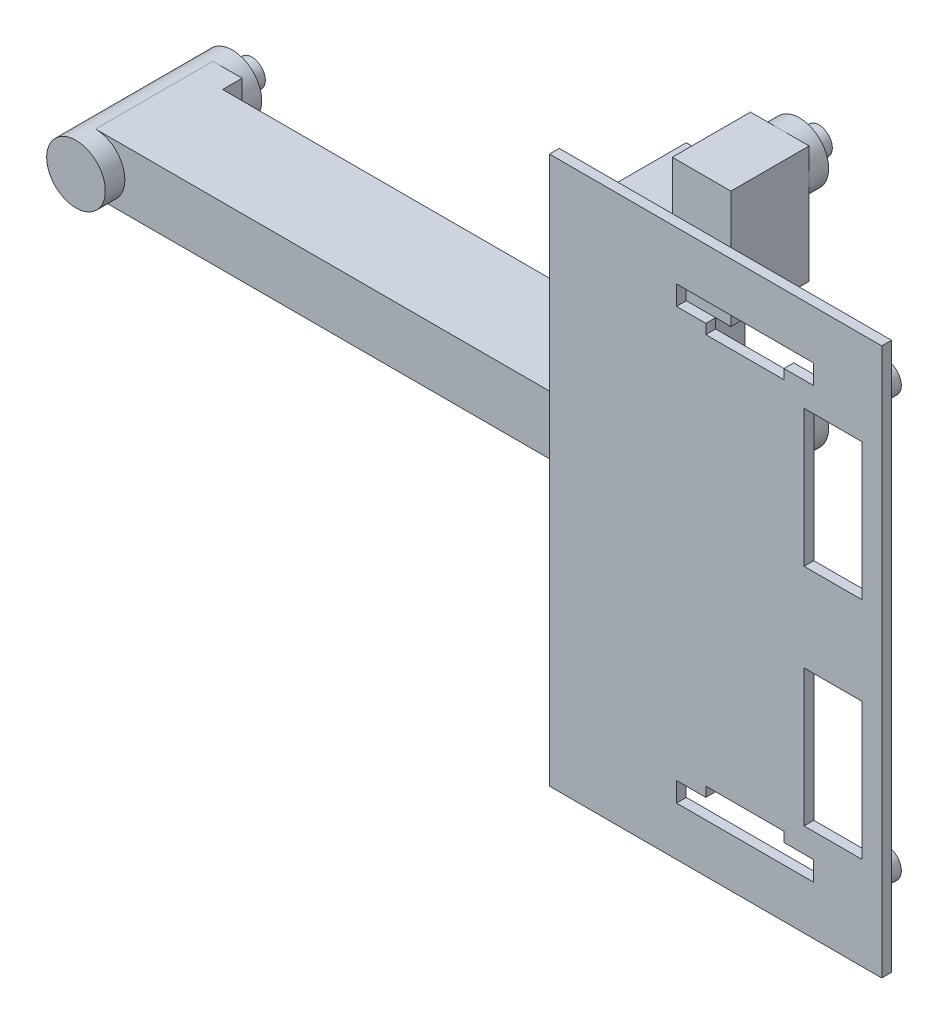
SolidWorks part; units mm, degrees
ref_plane "前视基准面" through (0, 0, 0) normal (0, 0, 1) x (1, 0, 0)
ref_plane "上视基准面" through (0, 0, 0) normal (0, 1, 0) x (1, 0, 0)
ref_plane "右视基准面" through (0, 0, 0) normal (1, 0, 0) x (0, 0, -1)
sketch "草图1" plane through (0, 0, 0) normal (0, 0, 1) x (1, 0, 0)
  line L1 (-32.5, 3) -> (32.5, 3)
  line L2 (-32.5, 3) -> (-32.5, -3)
  line L3 (-32.5, -3) -> (32.5, -3)
  line L4 (32.5, 3) -> (32.5, -3)
  line L5 (-32.5, 3) -> (32.5, -3) construction
  line L6 (-32.5, -3) -> (32.5, 3) construction
  point P0 (0, 0)
  dimension "D1" = 65
  dimension "D2" = 6
extrude "凸台-拉伸1" add sketch "草图1" along normal blind 12
fillet "圆角4" radius 3 1 edges at (-32.5, -3, 6)
fillet "圆角5" radius 3 1 edges at (-32.5, 3, 6)
sketch "草图7" plane through (0, 0, 0) normal (0, 0, -1) x (-1, 0, 0)
  circle A0 centre (29.5, 0) radius 1.375
extrude "凸台-拉伸2" add sketch "草图7" along normal blind 4 contours A0
sketch "草图8" plane through (0, 0, 0) normal (0, 0, -1) x (-1, 0, 0)
  circle A0 centre (29.5, 0) radius 3
extrude "凸台-拉伸3" add sketch "草图8" along normal blind 2
sketch "草图9" plane through (0, 0, 12) normal (0, 0, 1) x (1, 0, 0)
  circle A0 centre (-29.5, 0) radius 3
extrude "凸台-拉伸4" add sketch "草图9" along normal blind 4
sketch "草图10" plane through (0, 0, 0) normal (0, 0, -1) x (-1, 0, 0)
  circle A0 centre (-29.5, 0) radius 3
extrude "凸台-拉伸5" add sketch "草图10" along normal blind 2
sketch "草图11" plane through (0, 0, -2) normal (0, 0, -1) x (-1, 0, 0)
  circle A0 centre (-29.5, 0) radius 1.375
extrude "凸台-拉伸6" add sketch "草图11" along normal blind 2
sketch "草图12" plane through (0, 0, 12) normal (0, 0, 1) x (1, 0, 0)
  line L0 (32.5, -3) -> (32.5, 3)
  line L1 (32.5, -3) -> (26.5, -3)
  line L2 (32.5, 3) -> (26.5, 3)
  line L3 (26.5, -3) -> (26.5, 3)
extrude "凸台-拉伸7" add sketch "草图12" along normal blind 2
sketch "草图13" plane through (0, 0, 0) normal (0, 0, -1) x (-1, 0, 0)
  line L1 (-32.5, -3) -> (-26.5, -3)
  line L2 (-32.5, -3) -> (-32.5, 27)
  line L3 (-32.5, 27) -> (-26.5, 27)
  line L4 (-26.5, -3) -> (-26.5, 27)
  dimension "D1" = 6
  dimension "D2" = 30
extrude "凸台-拉伸8" add sketch "草图13" against normal blind 2
sketch "草图14" plane through (0, 0, 0) normal (0, 0, -1) x (-1, 0, 0)
  circle A0 centre (-29.5, 24) radius 3
extrude "凸台-拉伸9" add sketch "草图14" along normal blind 2
sketch "草图15" plane through (0, 0, 0) normal (0, 0, -1) x (-1, 0, 0)
  circle A0 centre (-29.5, 24) radius 1.375
extrude "凸台-拉伸10" add sketch "草图15" along normal blind 4
sketch "草图18" plane through (0, 0, 12) normal (0, 0, 1) x (1, 0, 0)
  line L0 (32.5, -3) -> (32.5, 3) construction
  line L1 (18.93, 27) -> (24.93, 27)
  line L2 (18.93, 27) -> (18.93, -3)
  line L3 (18.93, -3) -> (24.93, -3)
  line L4 (24.93, 27) -> (24.93, -3)
  line L5 (18.93, 27) -> (24.93, -3) construction
  line L6 (18.93, -3) -> (24.93, 27) construction
  line L7 (26.5, -3) -> (32.5, -3) construction
  point P0 (21.93, 12)
  point P9 (21.93, -3)
  dimension "D1" = 30
  dimension "D2" = 6
  dimension "D3" = 7.57
  dimension "D4" = 0
extrude "凸台-拉伸11" add sketch "草图18" along normal blind 4
sketch "草图19" plane through (0, 0, 12) normal (0, 0, -1) x (-1, 0, 0)
  line L1 (-18.93, 27) -> (-24.93, 27)
  line L2 (-18.93, 27) -> (-18.93, -3)
  line L3 (-18.93, -3) -> (-24.93, -3)
  line L4 (-24.93, 27) -> (-24.93, -3)
extrude "凸台-拉伸12" add sketch "草图19" along normal blind 10
sketch "草图29" plane through (0, 0, 16) normal (0, 0, 1) x (1, 0, 0)
  line L1 (24.93, 27) -> (-43.8103, 27)
  line L2 (24.93, 27) -> (24.93, -9.6985)
  line L3 (24.93, -9.6985) -> (-43.8103, -9.6985)
  line L4 (-43.8103, 27) -> (-43.8103, -9.6985)
extrude "切除-拉伸3" cut sketch "草图29" against normal blind 2
sketch "草图30" plane through (0, 0, 14) normal (0, 0, 1) x (1, 0, 0)
  line L1 (32.5, -3) -> (24.93, -3)
  line L2 (32.5, -3) -> (32.5, 3)
  line L3 (32.5, 3) -> (24.93, 3)
  line L4 (24.93, -3) -> (24.93, 3)
extrude "切除-拉伸4" cut sketch "草图30" against normal blind 12
sketch "草图31" plane through (0, 0, 2) normal (0, 0, -1) x (-1, 0, 0)
  line L1 (-18.93, 27) -> (-26.5, 27)
  line L2 (-18.93, 27) -> (-18.93, 3)
  line L3 (-18.93, 3) -> (-26.5, 3)
  line L4 (-26.5, 27) -> (-26.5, 3)
extrude "凸台-拉伸18" add sketch "草图31" along normal blind 2
sketch "草图32" plane through (0, 0, 0) normal (0, 0, -1) x (-1, 0, 0)
  line L0 (-32.5, 0) -> (-32.5, 24) construction
  line L1 (-32.5, 21) -> (-26.5, 21)
  line L2 (-32.5, 21) -> (-32.5, 3)
  line L3 (-32.5, 3) -> (-26.5, 3)
  line L4 (-26.5, 21) -> (-26.5, 3)
  circle A0 centre (-29.5, 24) radius 3 construction
  dimension "D3" = 3
  dimension "D1" = 6
  dimension "D2" = 18
extrude "切除-拉伸6" cut sketch "草图32" against normal blind 2
sketch "草图33" plane through (0, 0, 2) normal (0, 0, 1) x (1, 0, 0)
  line L0 (24.93, 27) -> (24.93, -3) construction
  line L1 (26.5, 21) -> (24.93, 21)
  line L2 (26.5, 21) -> (26.5, 3)
  line L3 (26.5, 3) -> (24.93, 3)
  line L4 (24.93, 21) -> (24.93, 3)
  dimension "D1" = 18
extrude "切除-拉伸7" cut sketch "草图33" against normal blind 2
sketch "草图34" plane through (0, 0, 14) normal (0, 0, 1) x (1, 0, 0)
  line L1 (18.93, 27) -> (52.93, 27)
  line L2 (18.93, 27) -> (18.93, -23)
  line L3 (18.93, -23) -> (52.93, -23)
  line L4 (52.93, 27) -> (52.93, -23)
  dimension "D1" = 50
  dimension "D2" = 34
extrude "凸台-拉伸19" add sketch "草图34" against normal blind 1
sketch "草图35" plane through (0, 0, 13) normal (0, 0, -1) x (-1, 0, 0)
  line L0 (-52.93, 27) -> (-24.93, 27) construction
  line L1 (-52.93, -23) -> (-52.93, 27) construction
  line L2 (-18.93, -23) -> (-52.93, -23) construction
  line L3 (-18.93, -3) -> (-18.93, -23) construction
  circle A0 centre (-49.43, 23.5) radius 1.5
  circle A1 centre (-49.43, -19.5) radius 1.5
  circle A2 centre (-28.43, -19.5) radius 1.5
  circle A3 centre (-28.43, 23.5) radius 1.5
  dimension "D1" = 3.5
  dimension "D3" = 3.5
  dimension "D5" = 9.5
  dimension "D2" = 3.5
  dimension "D4" = 3.5
extrude "凸台-拉伸20" add sketch "草图35" along normal blind 2
sketch "草图36" plane through (0, 0, 13) normal (0, 0, -1) x (-1, 0, 0)
  line L0 (-52.93, 27) -> (-24.93, 27) construction
  line L1 (-47.93, 27) -> (-29.93, 27)
  line L2 (-47.93, 27) -> (-47.93, 23)
  line L3 (-47.93, 23) -> (-29.93, 23)
  line L4 (-29.93, 27) -> (-29.93, 23)
  circle A0 centre (-49.43, 23.5) radius 1.5 construction
  circle A1 centre (-28.43, -19.5) radius 1.5 construction
  dimension "D1" = 1.5
  dimension "D2" = 1.5
  dimension "D3" = 4
extrude "切除-拉伸8" cut sketch "草图36" against normal blind 3
sketch "草图37" plane through (0, 0, 13) normal (0, 0, -1) x (-1, 0, 0)
  line L0 (-29.93, -23) -> (-47.93, -23)
  line L1 (-29.93, -23) -> (-29.93, -19)
  line L2 (-47.93, -23) -> (-47.93, -19)
  line L3 (-29.93, -19) -> (-47.93, -19)
  line L4 (-18.93, -23) -> (-52.93, -23) construction
  dimension "D1" = 4
extrude "切除-拉伸9" cut sketch "草图37" against normal blind 3
sketch "草图38" plane through (0, 0, 13) normal (0, 0, -1) x (-1, 0, 0)
  line L0 (-52.93, -23) -> (-52.93, 27) construction
  line L1 (-52.93, 20.5) -> (-44.9804, 20.5)
  line L2 (-52.93, 20.5) -> (-52.93, -16.5)
  line L3 (-52.93, -16.5) -> (-44.9804, -16.5)
  line L4 (-44.9804, 20.5) -> (-44.9804, -16.5)
  circle A0 centre (-49.43, 23.5) radius 1.5 construction
  circle A1 centre (-49.43, -19.5) radius 1.5 construction
  dimension "D2" = 3
  dimension "D1" = 3
extrude "切除-拉伸10" cut sketch "草图38" against normal blind 3
sketch "草图39" plane through (0, 0, 13) normal (0, 0, -1) x (-1, 0, 0)
  line L1 (-52.93, 20.5) -> (-50.93, 20.5)
  line L2 (-52.93, 20.5) -> (-52.93, -18.2774)
  line L3 (-52.93, -18.2774) -> (-50.93, -18.2774)
  line L4 (-50.93, 20.5) -> (-50.93, -18.2774)
extrude "凸台-拉伸21" add sketch "草图39" against normal blind 1
sketch "草图40" plane through (0, 0, 13) normal (0, 0, -1) x (-1, 0, 0)
  line L1 (-47.93, 27) -> (-28.0386, 27)
  line L2 (-47.93, 27) -> (-47.93, 25)
  line L3 (-47.93, 25) -> (-28.0386, 25)
  line L4 (-28.0386, 27) -> (-28.0386, 25)
extrude "凸台-拉伸22" add sketch "草图40" against normal blind 1
sketch "草图41" plane through (0, 0, 13) normal (0, 0, -1) x (-1, 0, 0)
  line L0 (-47.93, -19.5) -> (-47.93, -23) construction
  line L1 (-47.93, -21) -> (-29.93, -21)
  line L2 (-47.93, -21) -> (-47.93, -23)
  line L3 (-47.93, -23) -> (-29.93, -23)
  line L4 (-29.93, -21) -> (-29.93, -23)
extrude "凸台-拉伸23" add sketch "草图41" against normal blind 1
sketch "草图42" plane through (0, 0, 13) normal (0, 0, -1) x (-1, 0, 0)
  line L0 (-50.93, -16.5) -> (-50.93, 20.5) construction
  line L1 (-50.93, 5.3498) -> (-44.9804, 5.3498)
  line L2 (-50.93, 5.3498) -> (-50.93, -2.4362)
  line L3 (-50.93, -2.4362) -> (-44.9804, -2.4362)
  line L4 (-44.9804, 5.3498) -> (-44.9804, -2.4362)
  line L5 (-44.9804, -16.5) -> (-44.9804, 20.5) construction
extrude "凸台-拉伸24" add sketch "草图42" against normal blind 1
sketch "草图43" plane through (0, 0, 13) normal (0, 0, -1) x (-1, 0, 0)
  line L0 (-29.93, -21) -> (-47.93, -21) construction
  line L1 (-47.93, -19) -> (-45.93, -19)
  line L2 (-47.93, -19) -> (-47.93, -21)
  line L3 (-47.93, -21) -> (-45.93, -21)
  line L4 (-45.93, -19) -> (-45.93, -21)
  line L5 (-47.93, 23) -> (-29.93, 23) construction
  line L6 (-29.93, -19) -> (-31.93, -19)
  line L7 (-29.93, -19) -> (-29.93, -21)
  line L8 (-29.93, -21) -> (-31.93, -21)
  line L9 (-31.93, -19) -> (-31.93, -21)
  line L10 (-47.93, 25) -> (-45.93, 25)
  line L11 (-47.93, 25) -> (-47.93, 23)
  line L12 (-47.93, 23) -> (-45.93, 23)
  line L13 (-45.93, 25) -> (-45.93, 23)
  line L15 (-29.93, 25) -> (-31.93, 25)
  line L16 (-29.93, 25) -> (-29.93, 23)
  line L17 (-29.93, 23) -> (-31.93, 23)
  line L18 (-31.93, 25) -> (-31.93, 23)
  dimension "D1" = 2
  dimension "D2" = 2
  dimension "D3" = 2
  dimension "D4" = 2
extrude "凸台-拉伸25" add sketch "草图43" against normal blind 1
sketch "草图44" plane through (0, 0, 13) normal (0, 0, -1) x (-1, 0, 0)
  line L1 (-52.93, -23) -> (-18.93, -23)
  line L2 (-52.93, -23) -> (-52.93, -29)
  line L3 (-52.93, -29) -> (-18.93, -29)
  line L4 (-18.93, -23) -> (-18.93, -29)
  dimension "D1" = 6
extrude "凸台-拉伸26" add sketch "草图44" against normal blind 1
sketch "草图45" plane through (0, 0, 14) normal (0, 0, 1) x (1, 0, 0)
  line L2 (44.9804, 5.3498) -> (44.9804, 20.5) construction
  line L3 (50.93, 5.3498) -> (44.9804, 5.3498)
  line L4 (50.93, 5.3498) -> (50.93, 6.5)
  line L5 (50.93, 6.5) -> (44.9804, 6.5)
  line L6 (44.9804, 5.3498) -> (44.9804, 6.5)
  line L7 (44.9804, 20.5) -> (50.93, 20.5) construction
  line L8 (50.93, -16.5) -> (50.93, -2.4362) construction
  line L10 (44.9804, -2.4362) -> (50.93, -2.4362)
  line L11 (44.9804, -2.4362) -> (44.9804, -2.5)
  line L12 (44.9804, -2.5) -> (50.93, -2.5)
  line L13 (50.93, -2.4362) -> (50.93, -2.5)
  dimension "D1" = 14
  dimension "D2" = 14
extrude "凸台-拉伸27" add sketch "草图45" against normal blind 1
sketch "草图46" plane through (0, 0, 14) normal (0, 0, 1) x (1, 0, 0)
  line L0 (45.93, 23) -> (31.93, 23) construction
  line L1 (35.43, 23) -> (42.43, 23)
  line L2 (35.43, 23) -> (35.43, 22)
  line L3 (35.43, 22) -> (42.43, 22)
  line L4 (42.43, 23) -> (42.43, 22)
  line L5 (31.93, 25) -> (31.93, 23) construction
  line L6 (31.93, -19) -> (45.93, -19) construction
  line L7 (35.43, -19) -> (42.43, -19)
  line L8 (35.43, -19) -> (35.43, -18)
  line L9 (35.43, -18) -> (42.43, -18)
  line L10 (42.43, -19) -> (42.43, -18)
  line L11 (45.93, -21) -> (45.93, -19) construction
  dimension "D1" = 3.5
  dimension "D2" = 3.5
  dimension "D3" = 7
  dimension "D4" = 1
  dimension "D5" = 7
  dimension "D6" = 3.5
  dimension "D7" = 1
extrude "切除-拉伸11" cut sketch "草图46" against normal blind 11
sketch "草图47" plane through (0, 0, 2) normal (0, 0, 1) x (1, 0, 0)
  line L0 (24.93, 21) -> (32.5, 21) construction
  line L1 (24.93, 27) -> (29.93, 27)
  line L2 (24.93, 27) -> (24.93, 21)
  line L3 (24.93, 21) -> (29.93, 21)
  line L4 (29.93, 27) -> (29.93, 21)
  dimension "D1" = 5
extrude "凸台-拉伸28" add sketch "草图47" along normal blind 7
sketch "草图48" plane through (0, 0, 2) normal (0, 0, 1) x (1, 0, 0)
  line L1 (24.93, 3) -> (32.5, 3)
  line L2 (24.93, 3) -> (24.93, -3)
  line L3 (24.93, -3) -> (32.5, -3)
  line L4 (32.5, 3) -> (32.5, -3)
extrude "凸台-拉伸29" add sketch "草图48" along normal blind 2
sketch "草图49" plane through (0, 0, 13) normal (0, 0, -1) x (-1, 0, 0)
  line L0 (-45.93, -21) -> (-45.93, -19) construction
  line L1 (-45.93, -25) -> (-31.93, -25)
  line L2 (-45.93, -25) -> (-45.93, -23)
  line L3 (-45.93, -23) -> (-31.93, -23)
  line L4 (-31.93, -25) -> (-31.93, -23)
  line L5 (-31.93, -21) -> (-45.93, -21) construction
  line L6 (-31.93, -19) -> (-31.93, -21) construction
  line L7 (-42.43, -19) -> (-42.43, -18) construction
  line L8 (-35.43, -18) -> (-35.43, -19) construction
  line L9 (-42.43, -22) -> (-35.43, -22)
  line L10 (-42.43, -22) -> (-42.43, -23)
  line L11 (-42.43, -23) -> (-35.43, -23)
  line L12 (-35.43, -22) -> (-35.43, -23)
  line L13 (-42.43, 22) -> (-42.43, 23) construction
  line L14 (-35.43, 22) -> (-42.43, 22) construction
  line L15 (-42.43, 19) -> (-35.43, 19)
  line L16 (-42.43, 19) -> (-42.43, 18)
  line L17 (-42.43, 18) -> (-35.43, 18)
  line L18 (-35.43, 19) -> (-35.43, 18)
  line L19 (-45.93, 23) -> (-45.93, 25) construction
  line L20 (-45.93, 21) -> (-31.93, 21)
  line L21 (-45.93, 21) -> (-45.93, 19)
  line L22 (-45.93, 19) -> (-31.93, 19)
  line L23 (-31.93, 21) -> (-31.93, 19)
  line L24 (-31.93, 25) -> (-31.93, 23) construction
  line L25 (-50.93, -16.5) -> (-50.93, -2.5) construction
  line L26 (-44.9804, -16.5) -> (-44.9804, -2.5) construction
  line L27 (-50.93, -6.5) -> (-44.9804, -6.5)
  line L28 (-50.93, -6.5) -> (-50.93, -20.5)
  line L29 (-50.93, -20.5) -> (-44.9804, -20.5)
  line L30 (-44.9804, -6.5) -> (-44.9804, -20.5)
  line L31 (-44.9804, -2.5) -> (-50.93, -2.5) construction
  line L32 (-50.93, 6.5) -> (-50.93, 20.5) construction
  line L33 (-44.9804, 6.5) -> (-44.9804, 20.5) construction
  line L34 (-50.93, 16.5) -> (-44.9804, 16.5)
  line L35 (-50.93, 16.5) -> (-50.93, 2.5)
  line L36 (-50.93, 2.5) -> (-44.9804, 2.5)
  line L37 (-44.9804, 16.5) -> (-44.9804, 2.5)
  line L38 (-44.9804, 20.5) -> (-50.93, 20.5) construction
  point P6 (-45.93, -24)
  dimension "D1" = 0
  dimension "D2" = 2
  dimension "D3" = 4
  dimension "D4" = 0
  dimension "D5" = 1
  dimension "D6" = 0
  dimension "D7" = 1
  dimension "D8" = 4
  dimension "D9" = 2
  dimension "D10" = 0
  dimension "D11" = 14
  dimension "D12" = 4
  dimension "D13" = 14
  dimension "D14" = 4
sketch "草图50" plane through (0, 0, 13) normal (0, 0, -1) x (-1, 0, 0)
  line L1 (-51.68, 26.3114) -> (-25.0024, 26.3114)
  line L2 (-51.68, 26.3114) -> (-51.68, -25.1125)
  line L3 (-51.68, -25.1125) -> (-25.0024, -25.1125)
  line L4 (-25.0024, 26.3114) -> (-25.0024, -25.1125)
extrude "凸台-拉伸35" add sketch "草图50" against normal blind 1
sketch "草图52" plane through (0, 0, 13) normal (0, 0, -1) x (-1, 0, 0)
  circle A0 centre (-49.43, 19.5) radius 1.5
  circle A1 centre (-49.43, 23.5) radius 1.5 construction
  circle A2 centre (-28.43, 19.5) radius 1.5
  circle A3 centre (-49.43, -23.5) radius 1.5
  circle A4 centre (-49.43, -19.5) radius 1.5 construction
  circle A5 centre (-28.43, -23.5) radius 1.5
  dimension "D1" = 4
  dimension "D2" = 4
sketch "草图53" plane through (0, 0, 13) normal (0, 0, -1) x (-1, 0, 0)
  line L1 (-52.0421, 25.8285) -> (-23.4934, 25.8285)
  line L2 (-52.0421, 25.8285) -> (-52.0421, -26.0782)
  line L3 (-52.0421, -26.0782) -> (-23.4934, -26.0782)
  line L4 (-23.4934, 25.8285) -> (-23.4934, -26.0782)
extrude "切除-拉伸21" cut sketch "草图53" along normal blind 2
extrude "凸台-拉伸37" add sketch "草图52" along normal blind 2
extrude "切除-拉伸22" cut sketch "草图49" against normal blind 4
sketch "草图55" plane through (24.93, 0, 0) normal (1, 0, 0) x (0, 0, -1)
  line L0 (-13, 25.8285) -> (-13, 27) construction
  line L1 (-11, -3) -> (-13, -3)
  line L2 (-11, -3) -> (-11, 26.4143)
  line L3 (-11, 26.4143) -> (-13, 26.4143)
  line L4 (-13, -3) -> (-13, 26.4143)
extrude "凸台-拉伸40" add sketch "草图55" against normal blind 4
sketch "草图57" plane through (0, 0, 13) normal (0, 0, -1) x (-1, 0, 0)
  circle A0 centre (-49.4344, 20.5) radius 1.5
  circle A1 centre (-49.43, 19.5) radius 1.5 construction
  circle A2 centre (-28.4344, 20.5) radius 1.5
  circle A3 centre (-28.43, 19.5) radius 1.5 construction
  circle A4 centre (-28.43, 19.5) radius 1.5 construction
  circle A5 centre (-28.4323, -22.5) radius 1.5
  circle A6 centre (-28.43, -23.5) radius 1.5 construction
  circle A7 centre (-49.4344, -22.5) radius 1.5
  dimension "D1" = 1
  dimension "D2" = 1
  dimension "D3" = 21
  dimension "D4" = 1
  dimension "D5" = 1
sketch "草图58" plane through (0, 0, 13) normal (0, 0, -1) x (-1, 0, 0)
  line L1 (-25.787, -28.3114) -> (-51.3782, -28.3114)
  line L2 (-25.787, -28.3114) -> (-25.787, 22.6296)
  line L3 (-25.787, 22.6296) -> (-51.3782, 22.6296)
  line L4 (-51.3782, -28.3114) -> (-51.3782, 22.6296)
extrude "切除-拉伸23" cut sketch "草图58" along normal blind 4
extrude "凸台-拉伸41" add sketch "草图57" along normal blind 2
sketch "草图59" plane through (0, 0, 13) normal (0, 0, -1) x (-1, 0, 0)
  line L0 (-44.9804, -6.5) -> (-44.9804, -20.5) construction
  line L1 (-44.9804, -19.5) -> (-50.93, -19.5)
  line L2 (-44.9804, -19.5) -> (-44.9804, -5.5)
  line L3 (-44.9804, -5.5) -> (-50.93, -5.5)
  line L4 (-50.93, -19.5) -> (-50.93, -5.5)
  line L5 (-50.93, -20.5) -> (-50.93, -6.5) construction
  line L6 (-50.93, -20.5) -> (-44.9804, -20.5) construction
  line L7 (-44.9804, 16.5) -> (-44.9804, 2.5) construction
  line L8 (-44.9804, 3.5) -> (-50.93, 3.5)
  line L9 (-44.9804, 3.5) -> (-44.9804, 17.5)
  line L10 (-44.9804, 17.5) -> (-50.93, 17.5)
  line L11 (-50.93, 3.5) -> (-50.93, 17.5)
  line L12 (-50.93, 2.5) -> (-50.93, 16.5) construction
  line L13 (-50.93, 2.5) -> (-44.9804, 2.5) construction
  line L14 (-45.93, 21) -> (-45.93, 19) construction
  line L15 (-31.93, 21) -> (-31.93, 19) construction
  line L16 (-45.93, 20) -> (-31.93, 20)
  line L17 (-45.93, 20) -> (-45.93, 22)
  line L18 (-45.93, 22) -> (-31.93, 22)
  line L19 (-31.93, 20) -> (-31.93, 22)
  line L20 (-45.93, 21) -> (-31.93, 21) construction
  line L21 (-45.93, 19) -> (-42.43, 19) construction
  line L22 (-35.43, 19) -> (-35.43, 18) construction
  line L23 (-42.43, 19) -> (-35.43, 19)
  line L24 (-42.43, 19) -> (-42.43, 20)
  line L25 (-42.43, 20) -> (-35.43, 20)
  line L26 (-35.43, 19) -> (-35.43, 20)
  line L27 (-31.93, -25) -> (-31.93, -23) construction
  line L28 (-31.93, -24) -> (-45.93, -24)
  line L29 (-31.93, -24) -> (-31.93, -22)
  line L30 (-31.93, -22) -> (-45.93, -22)
  line L31 (-45.93, -24) -> (-45.93, -22)
  line L32 (-45.93, -25) -> (-45.93, -23) construction
  line L33 (-45.93, -25) -> (-31.93, -25) construction
  line L34 (-45.93, -23) -> (-42.43, -23) construction
  line L35 (-42.43, -22) -> (-42.43, -23) construction
  line L36 (-35.43, -22) -> (-42.43, -22)
  line L37 (-35.43, -22) -> (-35.43, -21)
  line L38 (-35.43, -21) -> (-42.43, -21)
  line L39 (-42.43, -22) -> (-42.43, -21)
  line L40 (-35.43, -22) -> (-35.43, -23) construction
  dimension "D1" = 14
  dimension "D2" = 1
  dimension "D3" = 14
  dimension "D4" = 1
  dimension "D5" = 1
  dimension "D6" = 1
  dimension "D7" = 0
  dimension "D8" = 1
  dimension "D9" = 1
  dimension "D10" = 0
  dimension "D11" = 0
  dimension "D12" = 0
  dimension "D13" = 1
sketch "草图60" plane through (0, 0, 13) normal (0, 0, -1) x (-1, 0, 0)
  line L1 (-52.4043, 25.2853) -> (-26.2699, 25.2853)
  line L2 (-52.4043, 25.2853) -> (-52.4043, -26.9835)
  line L3 (-52.4043, -26.9835) -> (-26.2699, -26.9835)
  line L4 (-26.2699, 25.2853) -> (-26.2699, -26.9835)
extrude "凸台-拉伸43" add sketch "草图60" against normal blind 1
extrude "切除-拉伸24" cut sketch "草图59" against normal blind 1
sketch "草图62" plane through (0, 0, 0) normal (0, 0, -1) x (-1, 0, 0)
  circle A0 centre (-28.5, 0) radius 3
  circle A1 centre (-29.5, 0) radius 1.375 construction
  dimension "D1" = 1
sketch "草图63" plane through (0, 0, 0) normal (0, 0, -1) x (-1, 0, 0)
  line L0 (-18.93, 27) -> (-29.5, 27) construction
  circle A0 centre (-28.5, 24) radius 3
  circle A1 centre (-29.5, 24) radius 3 construction
  dimension "D1" = 3
  dimension "D2" = 1
sketch "草图64" plane through (0, -3, 0) normal (0, -1, 0) x (1, 0, 0)
  line L0 (32.5, -2) -> (32.5, 0) construction
  line L1 (32.5, 0) -> (-22.296, 0)
  line L2 (32.5, 0) -> (32.5, -10.1972)
  line L3 (32.5, -10.1972) -> (-22.296, -10.1972)
  line L4 (-22.296, 0) -> (-22.296, -10.1972)
  line L5 (-29.5, 0) -> (29.5, 0) construction
  dimension "D1" = 0
extrude "切除-拉伸25" cut sketch "草图64" against normal blind 43
extrude "凸台-拉伸44" add sketch "草图62" along normal blind 2
extrude "凸台-拉伸45" add sketch "草图63" along normal blind 2 contours A0
sketch "草图65" plane through (0, 0, -2) normal (0, 0, -1) x (-1, 0, 0)
  circle A0 centre (-28.5, 24) radius 1.375
  circle A1 centre (-28.5, 24) radius 3 construction
  circle A3 centre (-28.5, 0) radius 3 construction
  circle A4 centre (29.5, 0) radius 3 construction
  circle A5 centre (-28.5, 0) radius 1.375
  dimension "D1" = 0
  dimension "D2" = 58
  dimension "D3" = 0
extrude "凸台-拉伸46" add sketch "草图65" along normal blind 2
sketch "草图66" plane through (0, 0, 0) normal (0, 0, -1) x (-1, 0, 0)
  line L0 (-28.5, 27) -> (-32.5, 27) construction
  line L1 (-32.5, -3) -> (-31.5, -3)
  line L2 (-32.5, -3) -> (-32.5, 27)
  line L3 (-32.5, 27) -> (-31.5, 27)
  line L4 (-31.5, -3) -> (-31.5, 27)
  dimension "D1" = 3
extrude "切除-拉伸26" cut sketch "草图66" against normal blind 5
sketch "草图67" plane through (0, 0, 0) normal (0, 0, -1) x (-1, 0, 0)
  line L0 (-18.93, 27) -> (-28.5, 27) construction
  line L1 (-25.5, 27) -> (-18.93, 27)
  line L2 (-25.5, 27) -> (-25.5, 21)
  line L3 (-25.5, 21) -> (-18.93, 21)
  line L4 (-18.93, 27) -> (-18.93, 21)
  line L5 (-18.93, 3) -> (-18.93, 27) construction
  circle A0 centre (-28.5, 24) radius 1.375 construction
  circle A1 centre (-28.5, 24) radius 3 construction
  dimension "D1" = 3
  dimension "D2" = 3
sketch "草图68" plane through (0, 27, 0) normal (0, 1, 0) x (1, 0, 0)
  line L1 (24.93, -9) -> (31.5, -9)
  line L2 (24.93, -9) -> (24.93, 0)
  line L3 (24.93, 0) -> (31.5, 0)
  line L4 (31.5, -9) -> (31.5, 0)
extrude "凸台-拉伸47" add sketch "草图68" against normal blind 12
extrude "切除-拉伸29" cut sketch "草图67" against normal blind 13 contours L3 L4 L1 L2
sketch "草图70" plane through (0, -3, 0) normal (0, -1, 0) x (1, 0, 0)
  line L0 (-29.5, 0) -> (28.5, 0) construction
  line L1 (24.93, 13) -> (18.93, 13)
  line L2 (24.93, 13) -> (24.93, 0)
  line L3 (24.93, 0) -> (18.93, 0)
  line L4 (18.93, 13) -> (18.93, 0)
  line L6 (18.93, 12) -> (-29.5, 12)
  line L7 (18.93, 12) -> (18.93, 0)
  line L8 (18.93, 0) -> (-29.5, 0)
  line L9 (-29.5, 12) -> (-29.5, 0)
  line M4 (24.93, 4) -> (24.93, 13)
  line M5 (24.93, 13) -> (18.93, 13)
  line M6 (18.93, 13) -> (18.93, 12)
  line M7 (18.93, 12) -> (-29.5, 12)
  line M8 (-29.5, 12) -> (-29.5, 0)
  line M9 (-29.5, 0) -> (28.5, 0)
extrude "凸台-拉伸48" add sketch "草图70" against normal blind 7 contours L4 L2 M6 M9 M4 M5 | L4 M7 M8 M9
sketch "草图71" plane through (0, 3, 0) normal (0, 1, 0) x (1, 0, 0)
  line L1 (31.5, -4) -> (24.93, -4)
  line L2 (31.5, -4) -> (31.5, 0)
  line L3 (31.5, 0) -> (24.93, 0)
  line L4 (24.93, -4) -> (24.93, 0)
extrude "凸台-拉伸49" add sketch "草图71" along normal blind 1
sketch "草图72" plane through (0, 0, 0) normal (0, 0, -1) x (-1, 0, 0)
  line L0 (-31.5, -3) -> (-31.5, 0) construction
  line L1 (-31.5, 4) -> (-24.93, 4) construction
  circle A0 centre (-28.5, 1) radius 3
  dimension "D1" = 3
  dimension "D2" = 3
sketch "草图73" plane through (0, 0, 0) normal (0, 0, -1) x (-1, 0, 0)
  line L0 (29.5, 4) -> (29.5, 3) construction
  circle A0 centre (29.5, 1) radius 3
  dimension "D1" = 0
sketch "草图74" plane through (0, 0, 14) normal (0, 0, 1) x (1, 0, 0)
  circle A0 centre (-29.5, 0) radius 3
extrude "切除-拉伸30" cut sketch "草图74" against normal blind 32
sketch "草图75" plane through (0, 0, 0) normal (0, 0, -1) x (-1, 0, 0)
  line L0 (29.5, 4) -> (-18.93, 4) construction
  line L1 (29.5, -3) -> (26.367, -3)
  line L2 (29.5, -3) -> (29.5, 4)
  line L3 (29.5, 4) -> (26.367, 4)
  line L4 (26.367, -3) -> (26.367, 4)
  line L5 (29.5, -3) -> (-28.5, -3) construction
  dimension "D1" = 0
extrude "凸台-拉伸51" add sketch "草图75" against normal blind 12
sketch "草图76" plane through (31.5, 0, 0) normal (1, 0, 0) x (0, 0, -1)
  line L1 (0, 4) -> (8.5906, 4)
  line L2 (0, 4) -> (0, -5.1135)
  line L3 (0, -5.1135) -> (8.5906, -5.1135)
  line L4 (8.5906, 4) -> (8.5906, -5.1135)
extrude "切除-拉伸31" cut sketch "草图76" against normal blind 12
sketch "草图77" plane through (31.5, 0, 0) normal (1, 0, 0) x (0, 0, -1)
  line L0 (-13, -3) -> (-13, 21) construction
  line L1 (0, -3) -> (-13, -3)
  line L2 (0, -3) -> (0, -2)
  line L3 (0, -2) -> (-13, -2)
  line L4 (-13, -3) -> (-13, -2)
  dimension "D1" = 1
extrude "切除-拉伸32" cut sketch "草图77" against normal blind 124
extrude "凸台-拉伸52" add sketch "草图72" along normal blind 2
extrude "凸台-拉伸53" add sketch "草图73" against normal blind 14 and the other way blind 2 contours A0
sketch "草图78" plane through (0, 0, -2) normal (0, 0, -1) x (-1, 0, 0)
  circle A1 centre (-28.5, 1) radius 1.375
  circle A2 centre (29.5, 1) radius 1.375
extrude "凸台-拉伸54" add sketch "草图78" along normal blind 2
sketch "草图79" plane through (0, 0, 0) normal (0, 0, -1) x (-1, 0, 0)
  line L0 (-28.5, 4) -> (-24.93, 4) construction
  line L1 (-25.5, 4) -> (26.5, 4)
  line L2 (-25.5, 4) -> (-25.5, -2)
  line L3 (-25.5, -2) -> (26.5, -2)
  line L4 (26.5, 4) -> (26.5, -2)
  line L5 (29.5, -2) -> (-28.5, -2) construction
  circle A0 centre (29.5, 1) radius 1.375 construction
  circle A1 centre (-28.5, 1) radius 1.375 construction
  dimension "D2" = 3
  dimension "D1" = 3
extrude "切除-拉伸33" cut sketch "草图79" against normal blind 2
sketch "草图80" plane through (0, 0, 2) normal (0, 0, -1) x (-1, 0, 0)
  line L0 (-18.93, 4) -> (-18.93, 21) construction
  line L1 (-25.5, 4) -> (-18.93, 4)
  line L2 (-25.5, 4) -> (-25.5, 3)
  line L3 (-25.5, 3) -> (-18.93, 3)
  line L4 (-18.93, 4) -> (-18.93, 3)
  dimension "D1" = 0
  dimension "D2" = 1
extrude "凸台-拉伸55" add sketch "草图80" along normal blind 2
sketch "草图81" plane through (0, 0, 13) normal (0, 0, -1) x (-1, 0, 0)
  line L0 (-45.93, -22) -> (-42.43, -22) construction
  line L1 (-42.93, -22) -> (-34.93, -22)
  line L2 (-42.93, -22) -> (-42.93, -21)
  line L3 (-42.93, -21) -> (-34.93, -21)
  line L4 (-34.93, -22) -> (-34.93, -21)
  line L5 (-35.43, -21) -> (-42.43, -21) construction
  line L6 (-42.43, -22) -> (-42.43, -21) construction
  line L7 (-35.43, -22) -> (-35.43, -21) construction
  line L8 (-45.93, 20) -> (-42.43, 20) construction
  line L9 (-42.43, 19) -> (-35.43, 19) construction
  line L10 (-42.93, 20) -> (-34.93, 20)
  line L11 (-42.93, 20) -> (-42.93, 19)
  line L12 (-42.93, 19) -> (-34.93, 19)
  line L13 (-34.93, 20) -> (-34.93, 19)
  line L14 (-42.43, 19) -> (-42.43, 20) construction
  line L15 (-35.43, 19) -> (-35.43, 20) construction
  dimension "D1" = 0.5
  dimension "D2" = 0.5
  dimension "D3" = 0.5
  dimension "D4" = 0.5
extrude "切除-拉伸34" cut sketch "草图81" against normal blind 2
sketch "草图82" plane through (0, 27, 0) normal (0, 1, 0) x (1, 0, 0)
  line L0 (31.5, -9) -> (31.5, 0) construction
  line L1 (24.93, -9) -> (31.5, -9)
  line L2 (24.93, -9) -> (24.93, -8)
  line L3 (24.93, -8) -> (31.5, -8)
  line L4 (31.5, -9) -> (31.5, -8)
  dimension "D1" = 1
extrude "切除-拉伸35" cut sketch "草图82" against normal blind 45
sketch "草图83" plane through (0, 0, 11) normal (0, 0, -1) x (-1, 0, 0)
  circle A0 centre (-49.4344, 20.5) radius 1.5
  circle A1 centre (-49.4344, -22.5) radius 1.5
  circle A2 centre (-28.4323, -22.5) radius 1.5
  circle A3 centre (-28.4323, 20.5) radius 1.4979
extrude "凸台-拉伸56" add sketch "草图83" along normal blind 1
sketch "草图84" plane through (0, 0, 10) normal (0, 0, -1) x (-1, 0, 0)
  circle A0 centre (-28.1793, 20.3873) radius 2.7388
extrude "切除-拉伸36" cut sketch "草图84" against normal blind 3
sketch "草图85" plane through (0, 0, 13) normal (0, 0, -1) x (-1, 0, 0)
  circle A0 centre (-28.4344, 20.5) radius 1.5
  circle A1 centre (-49.4344, 20.5) radius 1.5 construction
  circle A2 centre (-28.4323, -22.5) radius 1.5 construction
  circle A3 centre (-49.4344, -22.5) radius 1.5 construction
  dimension "D1" = 21
  dimension "D2" = 43
  dimension "D3" = 21.0021
  dimension "D4" = 43
extrude "凸台-拉伸57" add sketch "草图85" along normal blind 3
